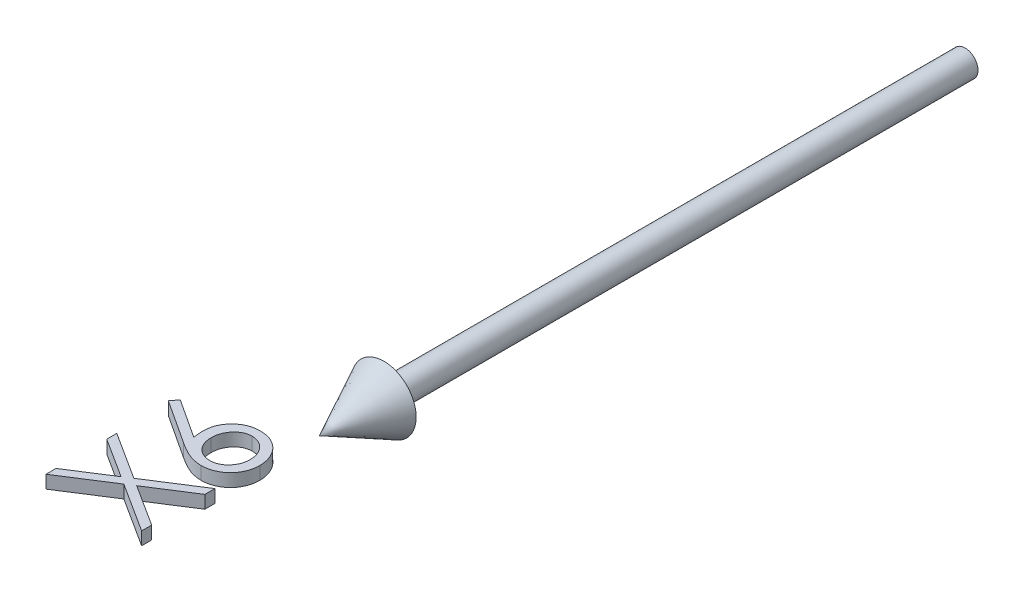
SolidWorks part; units mm, degrees
ref_plane "Front Plane" through (0, 0, 0) normal (0, 0, 1) x (1, 0, 0)
ref_plane "Top Plane" through (0, 0, 0) normal (0, 1, 0) x (1, 0, 0)
ref_plane "Right Plane" through (0, 0, 0) normal (1, 0, 0) x (0, 0, -1)
sketch "Sketch2" plane through (0, 0, 0) normal (0, 1, 0) x (1, 0, 0)
  line L0 (0, 41.95) -> (0, -114.4521) construction
  line L1 (-36.8894, 0) -> (41.4965, 0) construction
  line L2 (0, -100) -> (5, -90)
  line L3 (5, -90) -> (2, -90)
  line L4 (2, -90) -> (2, 0)
  line L5 (2, 0) -> (0, 0)
  line L6 (0, 0) -> (0, -100)
  dimension "D1" = 100
  dimension "D2" = 2
  dimension "D3" = 10
  dimension "D4" = 5
revolve "Revolve1" add sketch "Sketch2" angle 360 about L0
sketch "Sketch3" plane through (0, 0, 0) normal (0, 1, 0) x (1, 0, 0)
  line L0 (0, -103.9528) -> (0, -147.2622) construction
  line L1 (-18.6107, -118.3811) -> (18.3141, -118.3811) construction
  text T0 "X6\r\n\r\n" font "Century Gothic" height 15
extrude "Boss-Extrude1" add sketch "Sketch3" against normal blind 1 and the other way blind 1 separate body
equation "\"frame_arrow_length\"=100"
equation "\"D1@Sketch2\"=\"frame_arrow_length\""
equation "\"frame_arrow_odA\"=4"
equation "\"D2@Sketch2\"=\"frame_arrow_odA\"/2"
equation "\"frame_arrow_head_od\"=5"
equation "\"D4@Sketch2\"=\"frame_arrow_head_od\""
equation "\"frame_arrow_head_length\"=10"
equation "\"D3@Sketch2\"=\"frame_arrow_head_length\""
equation "\"tvarobot_theta1\"=30"
equation "\"link0_ringA_odA\"= 40"
equation "\"link0_ringA_odB\"= 25"
equation "\"link0_ringA_id\"= 20"
equation "\"link0_ringA_thickness\"= (\"link0_ringA_odB\" - \"link0_ringA_id\")/2"
equation "\"link0_ringA_height\"= 3"
equation "\"link0_ringA_heightA\"= 1.5"
equation "\"link0_ringA_heightB\"=\"link0_ringA_height\"-\"link0_ringA_heightA\""
equation "\"link0_ringB_odA\"= 40"
equation "\"link0_ringB_odB\"= 29"
equation "\"link0_ringB_id\"= \"link0_shaftA_bearing_id\"+1"
equation "\"link0_ringB_thickness\"= (\"link0_ringB_odB\" - \"link0_ringB_id\")/2"
equation "\"link0_ringB_height\"= 3"
equation "\"link0_ringB_heightA\"= 1.5"
equation "\"link0_ringB_heightB\"=\"link0_ringB_height\"-\"link0_ringB_heightA\""
equation "\"link0_shaftA_bearing_od\"=27"
equation "\"link0_shaftA_bearing_id\"=20"
equation "\"link0_shaftA_thrust_bearing_od\"=35"
equation "\"link0_shaftA_thrust_bearing_id\"=20.04"
equation "\"link0_shaftA_retaining_ring_id\"=18.5"
equation "\"link0_shaftA_retaining_ring_groove_width\"=1.5"
equation "\"link0_shaftA_spline_length\"=8.0"
equation "\"link0_shaftA_spline_depth\"=1.0"
equation "\"link0_shaftA_spline_width\"=4.0"
equation "\"link0_shaftA_odA\"=\"link0_shaftA_bearing_id\""
equation "\"link0_shaftA_odB\"=35"
equation "\"link0_shaftA_odC\"=\"link0_shaftA_bearing_id\""
equation "\"link0_shaftA_odD\"=\"link0_shaftA_odC\"-2*\"link0_shaftA_spline_depth\""
equation "\"link0_shaftA_odE\"=\"link0_shaftA_bearing_id\""
equation "\"link0_shaftA_odF\"=\"link0_shaftA_odE\"-2*\"link0_shaftA_spline_depth\""
equation "\"link0_shaftA_idA\"=10"
equation "\"link0_shaftA_idB\"=6"
equation "\"link0_shaftA_length\"=39.5"
equation "\"link0_shaftA_lengthA\"=8.0"
equation "\"link0_shaftA_lengthB\"=12.0"
equation "\"link0_shaftA_lengthC\"=35.0"
equation "\"link0_shaftA_lengthD\"=39.0"
equation "\"link0_shaftA_lengthE\"=\"link0_shaftA_length\"-\"link0_shaftA_lengthD\""
equation "\"link0_shaftA_offsetX\"=11"
equation "\"link0_shaftA_offsetY\"=0"
equation "\"link0_shaftA_bolt_pattern_dia\"=14"
equation "\"link0_motor_center_dist\"=26"
equation "\"link0_46t_pulley_spline_length\"=8"
equation "\"link0_46t_pulley_spline_depth\"=\"link0_shaftA_spline_depth\"*1.025"
equation "\"link0_46t_pulley_spline_width\"=\"link0_shaftA_spline_width\"*1.05"
equation "\"link0_46t_pulley_idA\"=\"link0_shaftA_bearing_id\"*1.025"
equation "\"link0_46t_pulley_idB\"=\"link0_46t_pulley_idA\"-2*\"link0_46t_pulley_spline_depth\""
equation "\"link0_shaftB_spline_length\"=10"
equation "\"link0_shaftB_spline_depth\"=1.0"
equation "\"link0_shaftB_spline_width\"=1.25"
equation "\"link0_shaftB_length\"=7"
equation "\"link0_shaftB_lengthA\"=1.5"
equation "\"link0_shaftB_lengthB\"=2.75"
equation "\"link0_shaftB_odA\"=32"
equation "\"link0_shaftB_odB\"=22"
equation "\"link0_shaftB_odC\"=20"
equation "\"link0_shaftB_idA\"=10"
equation "\"link0_shaftB_bolt_diameter\"=19"
equation "\"link0_shaftB_bearing_od\"=27"
equation "\"link0_shaftB_bearing_id\"=20"
equation "\"link0_motor_length\"=46.5"
equation "\"link0_motor_width\"=28.5"
equation "\"link0_motor_height\"=34"
equation "\"link0_motor_offset\"=8"
equation "\"link0_shellA_thickness\"=2.5"
equation "\"link0_shellB_thickness\"=\"link0_shellA_thickness\""
equation "\"link0_plateA_shellA_height\"=48"
equation "\"link0_shellA_width\" =\"link0_plateA_width\""
equation "\"link0_shellA_height\" = \"link0_plateA_shellA_height\"-\"link0_plateA_height\""
equation "\"link0_shellA_length\" = \"link0_plateA_lengthB\" "
equation "\"link0_shellB_length\"=\"link0_shellA_length\""
equation "\"link0_shellA_radius\" = 0.375*25.4"
equation "\"link0_shellA_radiusA\"= \"link0_plateA_radiusA\""
equation "\"link0_shellA_radiusB\"= \"link0_plateA_radiusB\""
equation "\"link0_shellA_radiusC\"= 3"
equation "\"link0_postA_height\"=7"
equation "\"link0_postA_width\"=16"
equation "\"link0_postA_length\"=20"
equation "\"link0_postA_posX\"=22"
equation "\"link0_postA_posY\"=17.5"
equation "\"link0_postA_pocket_width\"=6.0"
equation "\"link0_postA_pocket_length\"=2.5"
equation "\"link0_postA_pocket_depth\"=9"
equation "\"link0_postA_pocket_posZ\"=10"
equation "\"link0_postB_height\"=7"
equation "\"link0_postB_width\"=16"
equation "\"link0_postB_length\"=20"
equation "\"link0_postB_posX\"=22"
equation "\"link0_postB_posY\"=17.5"
equation "\"link0_postB_id\"=3.0"
equation "\"link0_postB_pocket_width\"=6.0"
equation "\"link0_postB_pocket_length\"=2.5"
equation "\"link0_postB_pocket_depth\"=9"
equation "\"link0_postB_pocket_posZ\"=10"
equation "\"link0_postC_height\"=7"
equation "\"link0_postC_width\"=16"
equation "\"link0_postC_length\"=20"
equation "\"link0_postC_posX\"=22"
equation "\"link0_postC_posY\"=17.5"
equation "\"link0_postC_id\"=3.0"
equation "\"link0_postC_pocket_width\"=6.0"
equation "\"link0_postC_pocket_length\"=2.5"
equation "\"link0_postC_pocket_depth\"=9"
equation "\"link0_postC_pocket_posZ\"=10"
equation "\"link0_postD_height\"=7"
equation "\"link0_postD_width\"=16"
equation "\"link0_postD_length\"=20"
equation "\"link0_postD_posX\"=22"
equation "\"link0_postD_posY\"=17.5"
equation "\"link0_postD_id\"=3.0"
equation "\"link0_postD_pocket_width\"=6.0"
equation "\"link0_postD_pocket_length\"=3.0"
equation "\"link0_postD_pocket_depth\"=9"
equation "\"link0_postD_pocket_posZ\"=10"
equation "\"link0_postE_height\"=5"
equation "\"link0_postE_width\"=16"
equation "\"link0_postE_length\"=\"link0_plateE_lengthA\"-\"link0_lip_height\""
equation "\"link0_postE_posZ\"=22"
equation "\"link0_postE_posX\"=17.5"
equation "\"link0_postE_posY\"=22"
equation "\"link0_postE_id\"=3.0"
equation "\"link0_postE_cbore_id\"=6.5"
equation "\"link0_postE_hole_id\"=3"
equation "\"link0_postF_posZ\"=22"
equation "\"link0_postF_posX\"=17.5"
equation "\"link0_postF_posY\"=\"link0_plateB_lengthA\"+4"
equation "\"link0_postF_id\"=3.0"
equation "\"link0_postF_cbore_id\"=6.5"
equation "\"link0_postF_hole_id\"=3"
equation "\"link0_postG_posZ\"=22"
equation "\"link0_postG_posX\"=17.5"
equation "\"link0_postG_posY\"=\"link0_plateB_lengthA\"+12"
equation "\"link0_postG_id\"=3.0"
equation "\"link0_postG_cbore_id\"=6.5"
equation "\"link0_postG_hole_id\"=3"
equation "\"link0_postHIJ_posY\"=6"
equation "\"link0_postH_posX\"=28"
equation "\"link0_postH_posY\"=20"
equation "\"link0_postH_posZ\"=20"
equation "\"link0_postH_length\"=10"
equation "\"link0_postI_posX\"=28"
equation "\"link0_postI_posY\"=20"
equation "\"link0_postI_posZ\"=135"
equation "\"link0_postI_length\"=10"
equation "\"link0_postJ_posX\"=28"
equation "\"link0_postJ_posY\"=20"
equation "\"link0_postJ_posZ\"=175"
equation "\"link0_postJ_length\"=10"
equation "\"link0_postK_posX\"=28"
equation "\"link0_postK_posY\"=20"
equation "\"link0_postK_posZ\"=175"
equation "\"link0_postK_length\"=10"
equation "\"link0_postL_posX\"=28"
equation "\"link0_postL_posY\"=20"
equation "\"link0_postL_posZ\"=135"
equation "\"link0_postL_length\"=10"
equation "\"link0_postM_posX\"=28"
equation "\"link0_postM_posY\"=20"
equation "\"link0_postM_posZ\"=35"
equation "\"link0_postM_length\"=10"
equation "\"link0_plateA_lengthA\"=30"
equation "\"link0_plateA_lengthB\"=150"
equation "\"link0_plateA_lengthC\"=30"
equation "\"link0_plateA_length\"=\"link0_plateA_lengthA\"+\"link0_plateA_lengthB\"+\"link0_plateA_lengthC\""
equation "\"link0_plateA_width\"=  68"
equation "\"link0_plateA_height\"= \"link0_plateA_radiusA\""
equation "\"link0_plateA_thickness\"=\"link0_shellA_thickness\""
equation "\"link0_plateA_radius\"= 9.5"
equation "\"link0_plateA_radiusA\"= 18"
equation "\"link0_plateA_radiusB\"= 18"
equation "\"link0_plateA_radiusC\"= 3"
equation "\"link0_plateB_length\"= 40"
equation "\"link0_plateB_width\"= \"link0_plateA_width\"*1.005"
equation "\"link0_plateB_height\"= \"link0_plateA_shellA_height\"*1.005"
equation "\"link0_plateB_lengthA\"=\"link0_lip_height\"+\"link0_plateD_thickness\"+\"link0_motor_mount_thickness\""
equation "\"link0_plateB_lengthB\"=\"link0_plateB_height\"-\"link0_plateB_lengthA\""
equation "\"link0_plateB_radiusA\"= \"link0_plateA_radiusA\""
equation "\"link0_plateB_radiusB\"= \"link0_plateA_radiusB\""
equation "\"link0_plateB_radiusC\"= 3"
equation "\"link0_plateB_idA\"=\"link0_shaftA_odC\"+1"
equation "\"link0_plateB_idB\"=\"link0_shaftA_bearing_od\"-2"
equation "\"link0_plateB_idC\"=\"link0_shaftA_bearing_od\"*1.005"
equation "\"link0_plateB_idD\"=\"link0_shaftA_thrust_bearing_od\"+1 "
equation "\"link0_plateB_depthA\"=1.0"
equation "\"link0_plateB_depthB\"=2.0"
equation "\"link0_plateB_depthC\"=8"
equation "\"link0_plateB_depthD\"=\"link0_plateB_length\"-\"link0_lip_height\"-\"link0_plateD_thickness\" "
equation "\"link0_plateC_length\"=\"link0_plateB_length\""
equation "\"link0_plateC_width\"= \"link0_plateB_width\""
equation "\"link0_plateC_height\"= .1*25.4"
equation "\"link0_plateA_hole_od\" = 0.1*25.4"
equation "\"link0_plateA_hole_delx\" = 0.5*25.4"
equation "\"link0_plateA_hole_delz\" = 0.75*25.4"
equation "\"link0_plateA_hole_offx\" = 0.0*25.4"
equation "\"link0_plateA_hole_offz\" = \"link0_plateA_length\"/2"
equation "\"link0_plateB_hole_od\" = 0.1*25.4"
equation "\"link0_plateB_hole_delx\"= 0.75*25.4"
equation "\"link0_plateB_hole_delz\"= 0.75*25.4"
equation "\"link0_plateB_hole_offx\"= 0.0*25.4"
equation "\"link0_plateB_hole_offz\"= 0.0*25.4"
equation "\"link0_plateC_hole_od\"= 0.1*25.4"
equation "\"link0_plateC_hole_delx\"= 0.75*25.4"
equation "\"link0_plateC_hole_delz\"= 0.75*25.4"
equation "\"link0_plateC_hole_offx\"= 0.0*25.4"
equation "\"link0_plateC_hole_offz\"= 0.0*25.4"
equation "\"link0_plateD_height\"=\"link0_plateB_height\"-2*\"link0_shellA_thickness\""
equation "\"link0_plateD_width\"=\"link0_plateB_width\"-2*\"link0_shellA_thickness\""
equation "\"link0_plateD_thickness\"=10"
equation "\"link0_plateD_radiusA\"=\"link0_plateB_radiusA\"-\"link0_shellA_thickness\""
equation "\"link0_plateD_odA\"= .375*25.4"
equation "\"link0_plateD_odB\"= .375*25.4"
equation "\"link0_plateD_bearing_id\"=20"
equation "\"link0_plateD_bearing_od\"=27"
equation "\"link0_plateE_radiusA\"=\"link0_plateA_radiusA\""
equation "\"link0_plateE_radiusB\"=\"link0_plateA_radiusB\""
equation "\"link0_plateE_radiusC\"=8.0"
equation "\"link0_plateE_length\"=30"
equation "\"link0_plateE_lengthA\"=16"
equation "\"link0_plateE_height\"=\"link0_plateB_height\""
equation "\"link0_plateE_width\"=\"link0_plateB_width\""
equation "\"link0_plateE_odA\"=\"gantry_coupler_id\"*0.99"
equation "\"link0_plateE_idA\"=\"link0_plateE_odA\"-20.0"
equation "\"link0_plateE_spline_depth\"=\"link0_poleA_spline_depth\"*1.05"
equation "\"link0_plateE_spline_width\"=\"link0_poleA_spline_width\"*1.075"
equation "\"link0_plateE_spline_length\"=\"link0_poleA_spline_length\""
equation "\"link0_plateE_coupler_length\"=46"
equation "\"link0_lip_height\"=5.0"
equation "\"link0_lip_thickness\"=2.0"
equation "\"link0_motor_mount_thickness\"=8.0"
equation "\"link0_motor_mount_idA\"=22"
equation "\"link0_motor_mount_idB\"=\"link0_shaftB_bearing_od\"*1.005"
equation "\"link0_motor_mount_idC\"=\"link0_shaftB_bearing_od\"-2"
equation "\"link0_motor_mount_depthA\"=5.5"
equation "\"link0_motor_mount_height\"=\"link0_plateD_height\""
equation "\"link0_motor_mount_width\"=\"link0_plateD_width\""
equation "\"link0_motor_mountL_height\"=36"
equation "\"link0_motor_mountL_heightA\"=12"
equation "\"link0_motor_mountL_length\"=50"
equation "\"link0_motor_mountL_lengthA\"=36"
equation "\"gantry_coupler_od\"=25.4*2.0"
equation "\"gantry_coupler_id\"=1.645*25.4"
equation "\"gantry_coupler_offsetX\"=\"link0_plateE_width\"/2"
equation "\"link0_poleA_odA\"=20"
equation "\"link0_poleA_odB\"=36"
equation "\"link0_poleA_idA\"=\"link0_poleA_odA\"-2*\"link0_poleA_thickness\""
equation "\"link0_poleA_idB\"=(\"link0_plateE_idA\"/2+1.5*\"link0_lip_thickness\")*1.04"
equation "\"link0_poleA_thickness\"=3.5"
equation "\"link0_poleA_length\"=100"
equation "\"link0_poleA_lengthA\"=18.5"
equation "\"link0_poleA_lengthB\"=80"
equation "\"link0_poleA_gasket_thickness\"=1.5"
equation "\"link0_poleA_spline_depth\"=1.0"
equation "\"link0_poleA_spline_width\"=4.0"
equation "\"link0_poleA_spline_length\"=10.0"
equation "\"link1_plateB_length\"=30"
equation "\"link1_lip_height\"=\"link0_lip_height\""
equation "\"link0_tension_plateA_width\"=12"
equation "\"link0_tension_plateA_lengthA\"=10.5"
equation "\"link0_tension_plateB_width\"=\"link0_tension_plateA_width\""
equation "\"link0_tension_plateB_lengthA\"=\"link0_tension_plateA_lengthA\""
equation "\"link0_tension_wheelA_posZ\"=7"
equation "\"link0_tension_wheelA_posX\"=\"link0_plateD_height\"/2-\"link0_tension_plateA_lengthA\""
equation "\"link0_m2_clear_hole_id\"=2.35"
equation "\"link0_m2_insert_hole_id\"=2.5"
equation "\"link0_m2_tap_hole_id\"=1.75"
equation "\"link0_m2_nut_socket_width\"=4.25"
equation "\"link0_m2_nut_socket_depth\"=2.5"
equation "\"link0_m2_cbore_id\"=3.75"
equation "\"link0_m2_cbore_depth\"=7"
equation "\"link0_m2_5_clear_hole_id\"=2.75"
equation "\"link0_m2_5_insert_hole_id\"=2.75"
equation "\"link0_m2_5_tap_hole_id\"=2.25"
equation "\"link0_m2_5_nut_socket_width\"=5.25"
equation "\"link0_m2_5_nut_socket_depth\"=2.5"
equation "\"link0_m2_5_cbore_id\"=4.75"
equation "\"link0_m2_5_cbore_depth\"=2.5"
equation "\"link0_m2_5_insert_access_length\"=6.0"
equation "\"link0_m2_5_insert_access_width\"=3.0"
equation "\"link0_m3_clear_hole_id\"=3.25"
equation "\"link0_m3_insert_hole_id\"=3"
equation "\"link0_m3_tap_hole_id\"=2.75"
equation "\"link0_m3_nut_socket_width\"=5.75"
equation "\"link0_m3_nut_socket_depth\"=4.0"
equation "\"link0_m3_cbore_id\"=5.75"
equation "\"link0_m3_cbore_depth\"=3.5"
equation "\"link0_m3_insert_access_length\"=4.5"
equation "\"link0_m3_insert_access_width\"=3.5"
equation "\"link0_rpi_mount_height\"=6"
equation "\"link0_rpi_mount_width\"=49"
equation "\"link0_rpi_mount_length\"=58"
equation "\"link0_rpi_mount_post_od\"=6"
equation "\"link0_rpi_mount_posZ\"=72"
equation "\"link0_rpi_mount_posX\"=11.5"
equation "\"link0_mcu_mount_height\"=5"
equation "\"link0_mcu_mount_width\"=49"
equation "\"link0_mcu_mount_length\"=58"
equation "\"link0_mcu_mount_post_od\"=6"
equation "\"link0_mcu_mount_posZ\"=164"
equation "\"link0_mcu_mount_posX\"=4"
equation "\"link0_pwr_mount_height\"=4"
equation "\"link0_pwr_mount_width\"=15.75"
equation "\"link0_pwr_mount_length\"=75.75"
equation "\"link0_pwr_mount_post_od\"=6"
equation "\"link0_pwr_mount_posZ\"=75"
equation "\"link0_pwr_mount_posX\"=16"
equation "\"link0_pwr_board_height\"=6"
equation "\"link0_pwr_board_width\"=21"
equation "\"link0_pwr_board_length\"=80"
